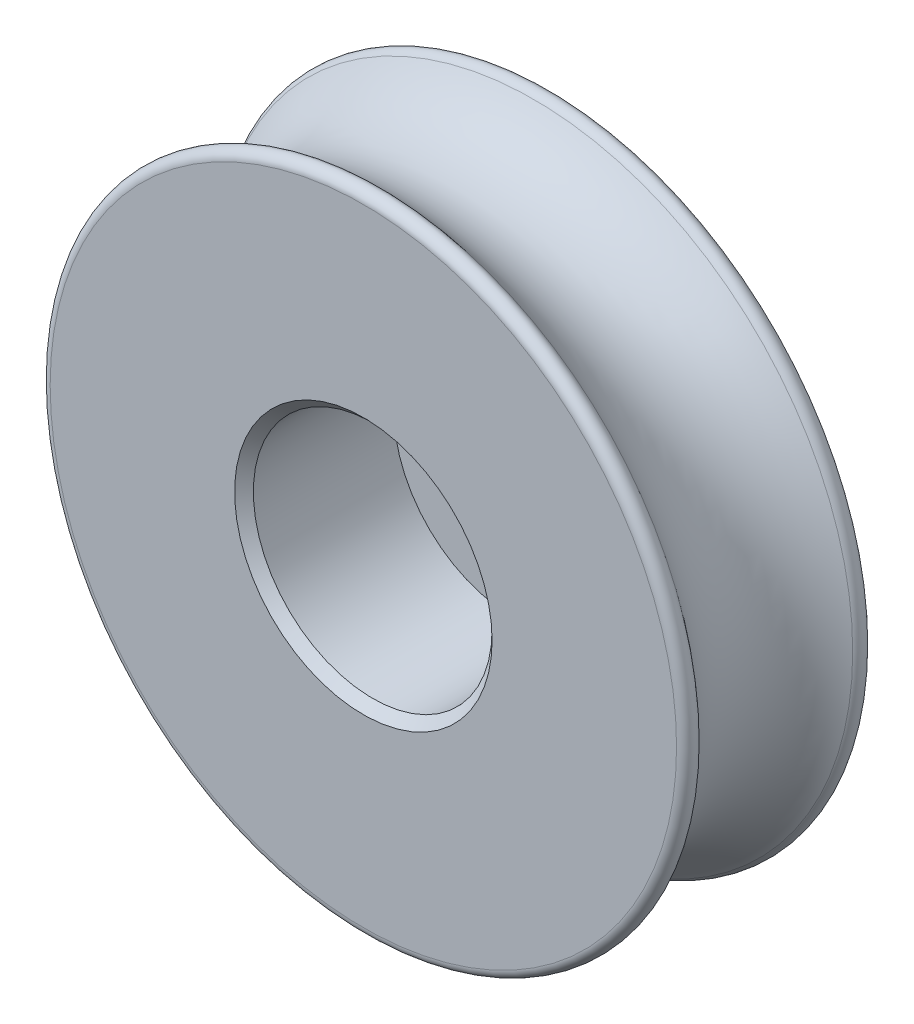
SolidWorks part; units mm, degrees
ref_plane "Front Plane" through (0, 0, 0) normal (0, 0, 1) x (1, 0, 0)
ref_plane "Top Plane" through (0, 0, 0) normal (0, 1, 0) x (1, 0, 0)
ref_plane "Right Plane" through (0, 0, 0) normal (1, 0, 0) x (0, 0, -1)
ref_axis "X Axis" through (-88.99, 0, 0) along (1, 0, 0)
ref_axis "Y Axis" through (0, 55, 0) along (0, -1, 0)
ref_axis "Z Axis" through (0, 0, -88.99) along (0, 0, 1)
sketch "Sketch2" plane through (0, 0, 0) normal (0, 1, 0) x (1, 0, 0)
  line L1 (1.1, 4) -> (7.55, 4)
  line L2 (7.55, 0) -> (2.55, 0)
  line L3 (2.55, 3.2) -> (2.55, 0)
  line L4 (0, 0) -> (0, 4) construction
  line L5 (2.55, 3.2) -> (1.1, 3.2)
  line L6 (1.1, 3.2) -> (1.1, 4)
  arc A0 (7.55, 4) -> (7.55, 0) centre (8.0653, 2) ccw
  dimension "D2" = 12
  dimension "D4" = 5
  dimension "D1" = 5.1
  dimension "D3" = 4
  dimension "D5" = 2.2
  dimension "D6" = 3.2
  dimension "D7" = 15.1
revolve "Revolve1" add sketch "Sketch2" angle 360 about L4
fillet "Fillet1" radius 0.2 2 edges at (7.55, 0, -4) (7.55, 0, 0)
chamfer "Chamfer2" distance 0.2 angle 45 2 edges at (1.1, 0, -4) (2.55, 0, 0)
